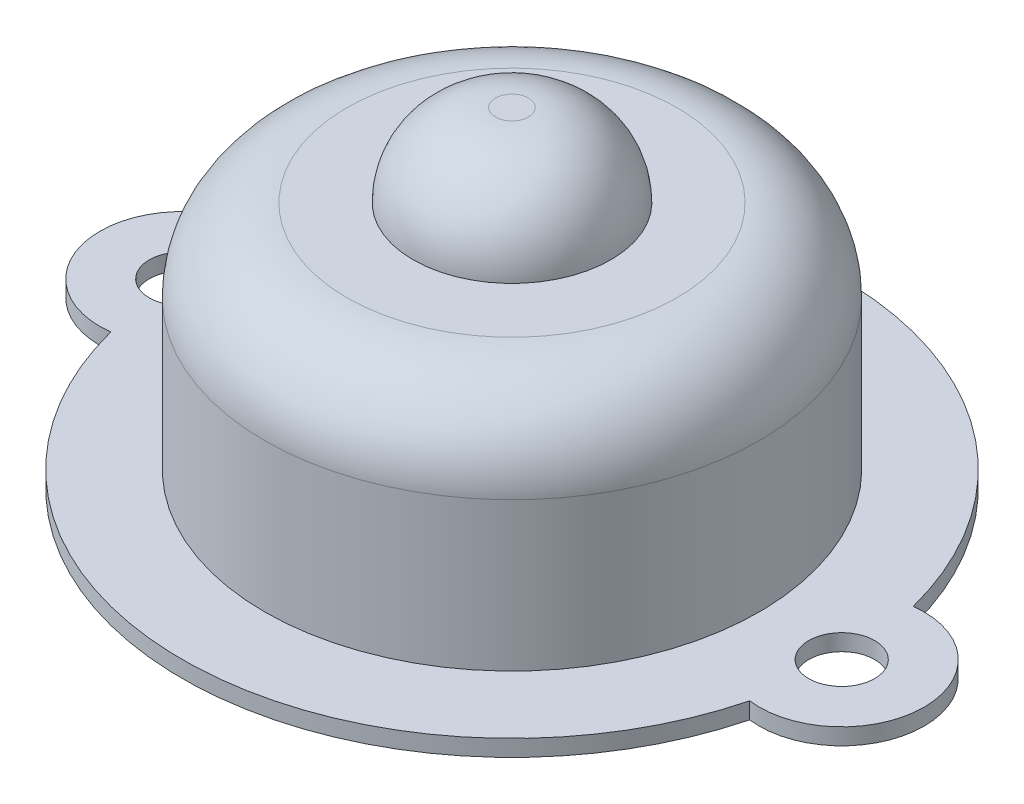
SolidWorks part; units mm, degrees
ref_plane "Front Plane" through (0, 0, 0) normal (0, 0, 1) x (1, 0, 0)
ref_plane "Top Plane" through (0, 0, 0) normal (0, 1, 0) x (1, 0, 0)
ref_plane "Right Plane" through (0, 0, 0) normal (1, 0, 0) x (0, 0, -1)
sketch "Sketch1" plane through (0, 0, 0) normal (0, 1, 0) x (1, 0, 0)
  arc A0 (-19.375, -4.9608) -> (19.375, -4.9608) centre (0, 0) ccw
  arc A1 (-19.375, 4.9608) -> (-19.375, -4.9608) centre (-20, 0) ccw
  arc A2 (19.375, -4.9608) -> (19.375, 4.9608) centre (20, 0) ccw
  arc A3 (19.375, 4.9608) -> (-19.375, 4.9608) centre (0, 0) ccw
  circle A4 centre (-20, 0) radius 2
  circle A5 centre (20, 0) radius 2
  dimension "D1" = 40
  dimension "D2" = 10
  dimension "D3" = 4
extrude "Boss-Extrude1" add sketch "Sketch1" along normal blind 1
sketch "Sketch2" plane through (0, 1, 0) normal (0, 1, 0) x (1, 0, 0)
  circle A0 centre (0, 0) radius 15
extrude "Boss-Extrude2" add sketch "Sketch2" along normal blind 14
fillet "Fillet1" radius 5 1 edges at (0, 15, 15)
sketch "Sketch3" plane through (0, 15, 0) normal (0, 1, 0) x (1, 0, 0)
  circle A0 centre (0, 0) radius 6
  dimension "D1" = 12
extrude "Boss-Extrude3" add sketch "Sketch3" along normal blind 5
fillet "Fillet2" radius 5 1 edges at (0, 20, 6)
